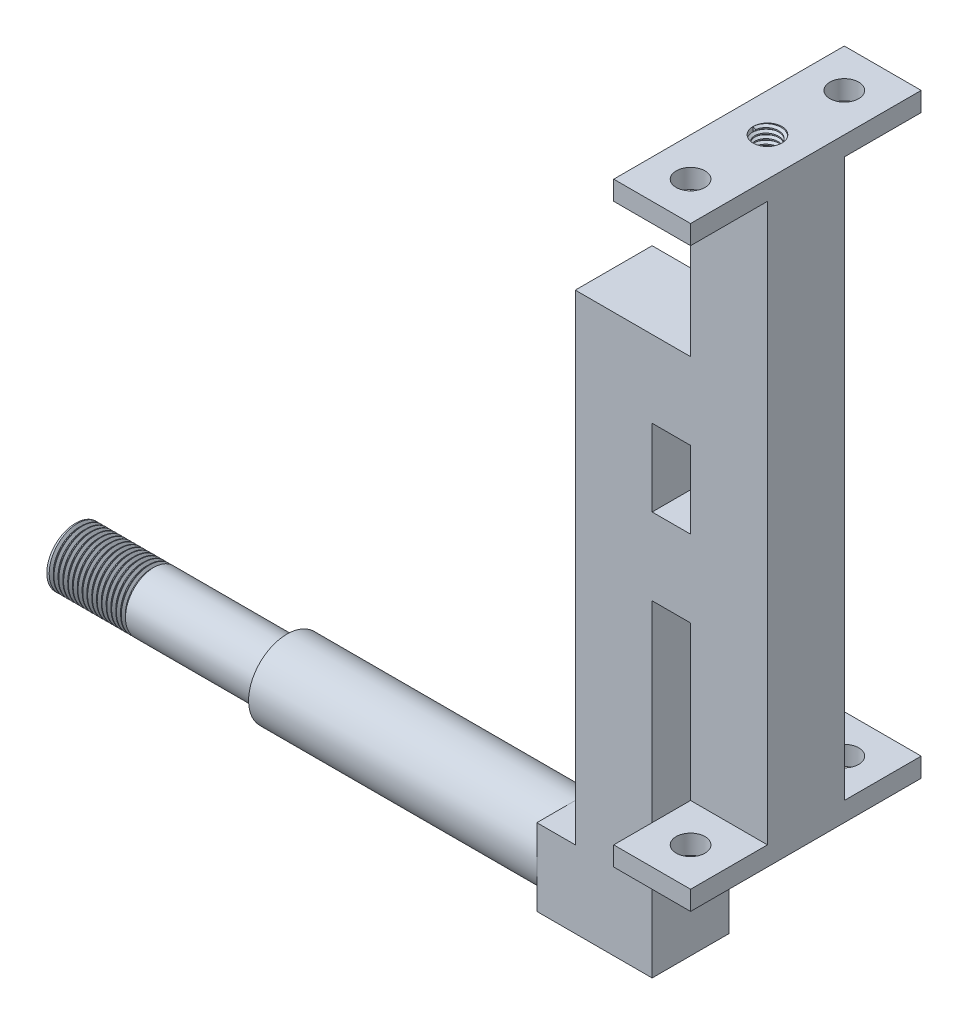
SolidWorks part; units mm, degrees
material "Plain Carbon Steel"
ref_plane "Front Plane" through (0, 0, 0) normal (0, 0, 1) x (1, 0, 0)
ref_plane "Top Plane" through (0, 0, 0) normal (0, 1, 0) x (1, 0, 0)
ref_plane "Right Plane" through (0, 0, 0) normal (1, 0, 0) x (0, 0, -1)
sketch "Sketch1" plane through (0, 0, 0) normal (0, 1, 0) x (1, 0, 0)
  line L1 (12.7, -12.7) -> (-12.7, -12.7)
  line L2 (12.7, -12.7) -> (12.7, 12.7)
  line L3 (12.7, 12.7) -> (-12.7, 12.7)
  line L4 (-12.7, -12.7) -> (-12.7, 12.7)
  line L5 (12.7, -12.7) -> (-12.7, 12.7) construction
  line L6 (12.7, 12.7) -> (-12.7, -12.7) construction
  line L7 (10.16, -10.16) -> (-10.16, -10.16)
  line L8 (10.16, -10.16) -> (10.16, 10.16)
  line L9 (10.16, 10.16) -> (-10.16, 10.16)
  line L10 (-10.16, -10.16) -> (-10.16, 10.16)
  line L11 (10.16, -10.16) -> (-10.16, 10.16) construction
  line L12 (10.16, 10.16) -> (-10.16, -10.16) construction
  point P0 (0, 0)
  point P5 (0, 0)
  dimension "D1" = 2.54
  dimension "1" = 25.4
extrude "Sq_Tb Extrude" add sketch "Sketch1" along normal blind 196.85
sketch "Sketch3" plane through (0, 196.85, 0) normal (0, 1, 0) x (1, 0, 0)
  line L0 (12.7, -12.7) -> (12.7, 12.7) construction
  line L1 (10.16, -10.16) -> (-10.16, -10.16)
  line L2 (10.16, -10.16) -> (10.16, 10.16)
  line L3 (10.16, 10.16) -> (-10.16, 10.16)
  line L4 (-10.16, -10.16) -> (-10.16, 10.16)
  line L5 (10.16, -10.16) -> (-10.16, 10.16) construction
  line L6 (10.16, 10.16) -> (-10.16, -10.16) construction
  line L7 (-12.7, 12.7) -> (12.7, 12.7)
  line L8 (-12.7, 12.7) -> (-12.7, 38.1)
  line L9 (-12.7, 38.1) -> (12.7, 38.1)
  line L10 (12.7, 12.7) -> (12.7, 38.1)
  line L11 (-12.7, 12.7) -> (12.7, 38.1) construction
  line L12 (-12.7, 38.1) -> (12.7, 12.7) construction
  line L13 (0, 0) -> (12.7, 0) construction
  line L14 (-12.7, -38.1) -> (12.7, -12.7) construction
  line L15 (-12.7, -12.7) -> (12.7, -38.1) construction
  line L16 (12.7, -12.7) -> (12.7, -38.1)
  line L17 (-12.7, -38.1) -> (12.7, -38.1)
  line L18 (-12.7, -12.7) -> (-12.7, -38.1)
  line L19 (-12.7, -12.7) -> (12.7, -12.7)
  circle A0 centre (0, 0) radius 4.7625
  circle A1 centre (0, 25.4) radius 4.7625
  circle A2 centre (0, -25.4) radius 4.7625
  point P0 (0, 0)
  point P13 (0, 25.4)
  point P26 (0, -25.4)
  dimension "D1" = 9.525
  dimension "D2" = 25.4
extrude "End Caps" add sketch "Sketch3" against normal blind 6.35
ref_plane "Mid-Plane" through (0, 98.425, 0) normal (0, 1, 0) x (1, 0, 0)
mirror "End Cap Mirror" about plane through (0, 98.425, 0) normal (0, 1, 0) of "End Caps"
thread "Top Thread" pitch 1.5875 method extrude profile "Thread Profile1" start angle 0, offset 0, length 0, pitch 1.5875, diameter 9.525
ref_plane "Plane2" through (-4.7625, 196.85, 0) normal (0, 0, 1) x (-1, 0, 0)
sketch "Thread Profile1" plane through (-4.7625, 196.85, 0) normal (0, 0, 1) x (-1, 0, 0)
  line L0 (0, 0) -> (0, 1.5875) construction
  line L11 (0, 0) -> (0, 1.3891)
  line L12 (0, 1.3891) -> (-0.8593, 0.893)
  line L13 (-0.8593, 0.893) -> (-0.8593, 0.4961)
  line L15 (-0.8593, 0.4961) -> (0, 0)
  line L17 (-0.8593, 0.6945) -> (0, 0.6945) construction
  point P2 (0, 0)
  dimension "Pitch" = 1.5875
  dimension "Profile_Angle" = 60
  dimension "Profile_Land" = 0.3969
  dimension "Profile_Height" = 0.8593
thread "Bottom Thread" pitch 1.5875 method extrude profile "Thread Profile2" start angle 0, offset 0, length 0, pitch 1.5875, diameter 9.525
ref_plane "Plane3" through (4.7625, 0, 0) normal (0, 0, 1) x (1, 0, 0)
sketch "Thread Profile2" plane through (4.7625, 0, 0) normal (0, 0, 1) x (1, 0, 0)
  line L0 (0, 0) -> (0, 1.5875) construction
  line L11 (0, 0) -> (0, 1.3891)
  line L12 (0, 1.3891) -> (-0.8593, 0.893)
  line L13 (-0.8593, 0.893) -> (-0.8593, 0.4961)
  line L15 (-0.8593, 0.4961) -> (0, 0)
  line L17 (-0.8593, 0.6945) -> (0, 0.6945) construction
  point P2 (0, 0)
  dimension "Pitch" = 1.5875
  dimension "Profile_Angle" = 60
  dimension "Profile_Land" = 0.3969
  dimension "Profile_Height" = 0.8593
sketch "Sketch9" plane through (0, 0, 0) normal (0, 0, 1) x (1, 0, 0)
  line L1 (-12.7, 190.5) -> (-12.7, 6.35) construction
  line L11 (-25.4, -50.8) -> (-63.5, -50.8)
  line L12 (-63.5, -50.8) -> (-63.5, -25.4)
  line L13 (-63.5, -25.4) -> (-63.1415, -25.4)
  line L15 (-63.5, -38.1) -> (0, -38.1) construction
  line L16 (0, -38.1) -> (0, 0) construction
  line L24 (-25.4, -25.4) -> (-25.4, -50.8)
  line L27 (-25.4, 107.95) -> (-50.8, 107.95) construction
  line L28 (-50.8, 107.95) -> (-50.8, -25.4)
  line L29 (-50.8, 107.95) -> (-50.8, 133.35)
  line L30 (-50.8, 133.35) -> (-12.7, 133.35)
  line L31 (-12.7, 190.5) -> (-12.7, 6.35) construction
  line L32 (-25.4, 107.95) -> (-12.7, 107.95)
  line L33 (-25.4, 57.15) -> (-12.7, 57.15)
  line L34 (-25.4, 82.55) -> (-12.7, 82.55)
  line L35 (-19.05, 82.55) -> (-19.05, 57.15) construction
  line L36 (-25.4, 107.95) -> (-50.8, 133.35) construction
  line L37 (-63.1415, -25.4) -> (-50.8, -25.4)
  line L38 (-50.8, -25.4) -> (-25.4, -25.4) construction
  line L39 (-50.8, -25.4) -> (-25.4, -50.8) construction
  line L40 (-12.7, 133.35) -> (-12.7, 107.95)
  line L41 (12.7, 190.5) -> (-12.7, 190.5) construction
  line L42 (-12.7, 0) -> (12.7, 0) construction
  line L43 (-25.4, 107.95) -> (-25.4, 82.55)
  line L44 (-25.4, 57.15) -> (-25.4, -25.4)
  line L45 (-12.7, 82.55) -> (-12.7, 57.15)
  dimension "D1" = 25.4
  dimension "D2" = 50.8
  dimension "D3" = 25.4
  dimension "D4" = 57.15
  dimension "D5" = 57.15
  dimension "D6" = 50.8
  dimension "D8" = 38.1
extrude "Sq_Tb Angles" add sketch "Sketch9" along normal blind 12.7 and the other way blind 12.7 contours L13 L12 L11 region at (-37.0114, 42.9079, 0)
sketch "Sketch11" plane through (0, 0, 0) normal (0, 0, 1) x (1, 0, 0)
  line L0 (-63.5, -38.1) -> (-228.6, -38.1)
  line L1 (-63.5, -50.8) -> (-63.5, -25.4) construction
  line L2 (-228.6, -38.1) -> (-228.6, -28.575)
  line L3 (-228.6, -28.575) -> (-158.75, -28.575)
  line L4 (-158.75, -28.575) -> (-158.75, -25.4)
  line L5 (-158.75, -25.4) -> (-63.5, -25.4)
  line L6 (-63.5, -25.4) -> (-63.5, -38.1)
  dimension "D1" = 12.7
  dimension "D2" = 9.525
  dimension "D3" = 95.25
  dimension "D4" = 69.85
revolve "Wheel Rod" add sketch "Sketch11" angle 360 about L0
thread "Wheel Threads" pitch 1.5875 method cut profile "Thread Profile3" start angle 0, offset 0, length 25.4, pitch 1.5875, diameter 19.05
ref_plane "Plane4" through (-228.6, -38.1, -9.525) normal (0, -1, 0) x (0, 0, -1)
sketch "Thread Profile3" plane through (-228.6, -38.1, -9.525) normal (0, -1, 0) x (0, 0, -1)
  line L0 (0, 0) -> (0, 1.5875) construction
  line L11 (0, 0) -> (0, 1.3891)
  line L12 (0, 1.3891) -> (-0.8593, 0.893)
  line L13 (-0.8593, 0.893) -> (-0.8593, 0.4961)
  line L15 (-0.8593, 0.4961) -> (0, 0)
  line L17 (-0.8593, 0.6945) -> (0, 0.6945) construction
  point P2 (0, 0)
  dimension "Pitch" = 1.5875
  dimension "Profile_Angle" = 60
  dimension "Profile_Land" = 0.3969
  dimension "Profile_Height" = 0.8593
ref_plane "Tie-Rod Mount Plane" through (0, 44.45, 0) normal (0, 1, 0) x (1, 0, 0)
